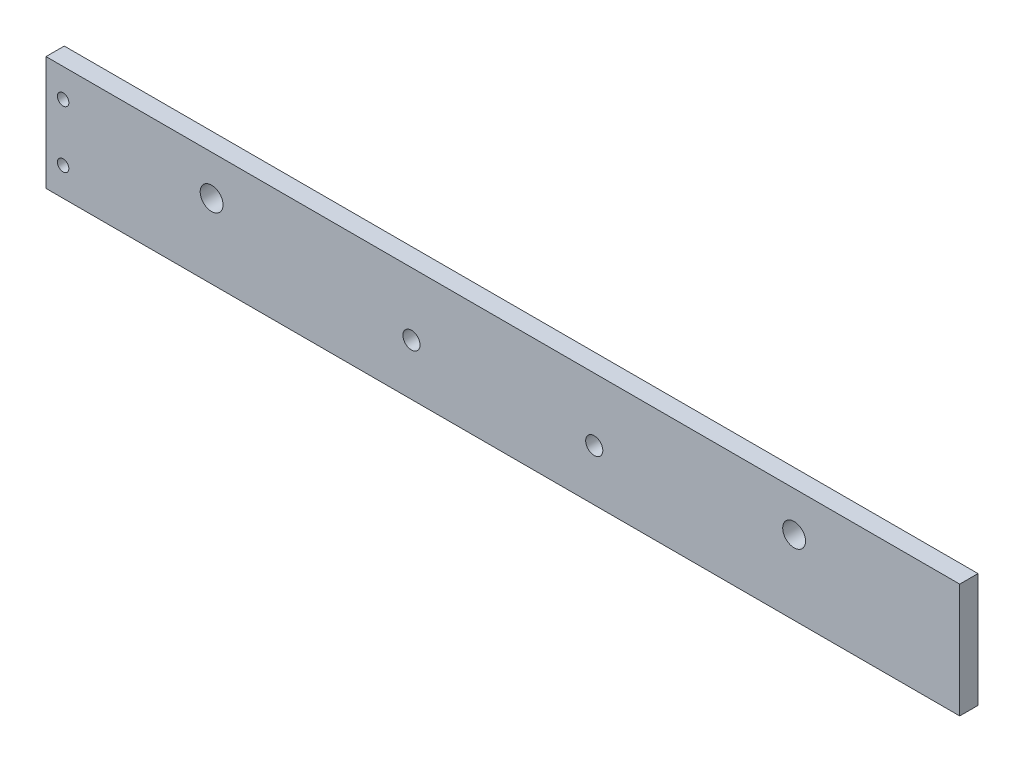
SolidWorks part; units mm, degrees
material "Balsa"
ref_plane "Front Plane" through (0, 0, 0) normal (0, 0, 1) x (1, 0, 0)
ref_plane "Top Plane" through (0, 0, 0) normal (0, 1, 0) x (1, 0, 0)
ref_plane "Right Plane" through (0, 0, 0) normal (1, 0, 0) x (0, 0, -1)
ref_plane "Plane1" through (0, 0, 10) normal (0, 0, 1) x (1, 0, 0)
sketch "Sketch2" plane through (0, -10, 10) normal (0, 0, -1) x (1, 0, 0)
  line L1 (0, -10) -> (160, -10)
  line L2 (0, -10) -> (0, 10)
  line L3 (0, 10) -> (160, 10)
  line L4 (160, -10) -> (160, 10)
  dimension "D1" = 20
  dimension "D2" = 160
extrude "Boss-Extrude1" add sketch "Sketch2" along normal blind 3.2
sketch "Sketch4" plane through (0, 0, 0) normal (0, 1, 0) x (1, 0, 0)
  line L0 (0, -10) -> (160, -10) construction
  line L1 (0, -6.8) -> (80, -6.8)
  line L2 (0, -6.8) -> (0, -10)
  line L3 (0, -10) -> (80, -10)
  line L4 (80, -6.8) -> (80, -10)
  line L5 (160, -6.8) -> (160, -10) construction
  dimension "D1" = 80
  dimension "D2" = 80
sketch "Sketch5" plane through (0, 0, 10) normal (0, 0, 1) x (1, 0, 0)
  line L0 (102, 2.15) -> (102, -20)
  line L1 (102, 0) -> (102, 4.3) construction
  line L2 (160, -20) -> (0, -20) construction
  line L3 (58, 2.15) -> (58, -20)
  line L4 (58, 0) -> (58, 4.3) construction
  line L7 (29, -7) -> (131, -7)
  line L9 (0, 0) -> (160, 0) construction
  circle A0 centre (131, -7) radius 2
  circle A1 centre (29, -7) radius 2
  dimension "D1" = 7
extrude "Cut-Extrude1" cut sketch "Sketch5" against normal through all both and the other way through all contours A0 | A1
sketch "Sketch6" plane through (0, 0, 10) normal (0, 0, 1) x (1, 0, 0)
  circle A0 centre (96, -11) radius 1.5
  circle A1 centre (64, -11) radius 1.5
  dimension "D1" = 32
extrude "Cut-Extrude2" cut sketch "Sketch6" against normal blind 10
sketch "Sketch7" plane through (0, 0, 10) normal (0, 0, 1) x (1, 0, 0)
  circle A0 centre (3, -15) radius 1
  circle A1 centre (3, -5) radius 1
  point P6 (0, 0)
  dimension "D1" = 2
extrude "Cut-Extrude3" cut sketch "Sketch7" against normal through all both and the other way through all
